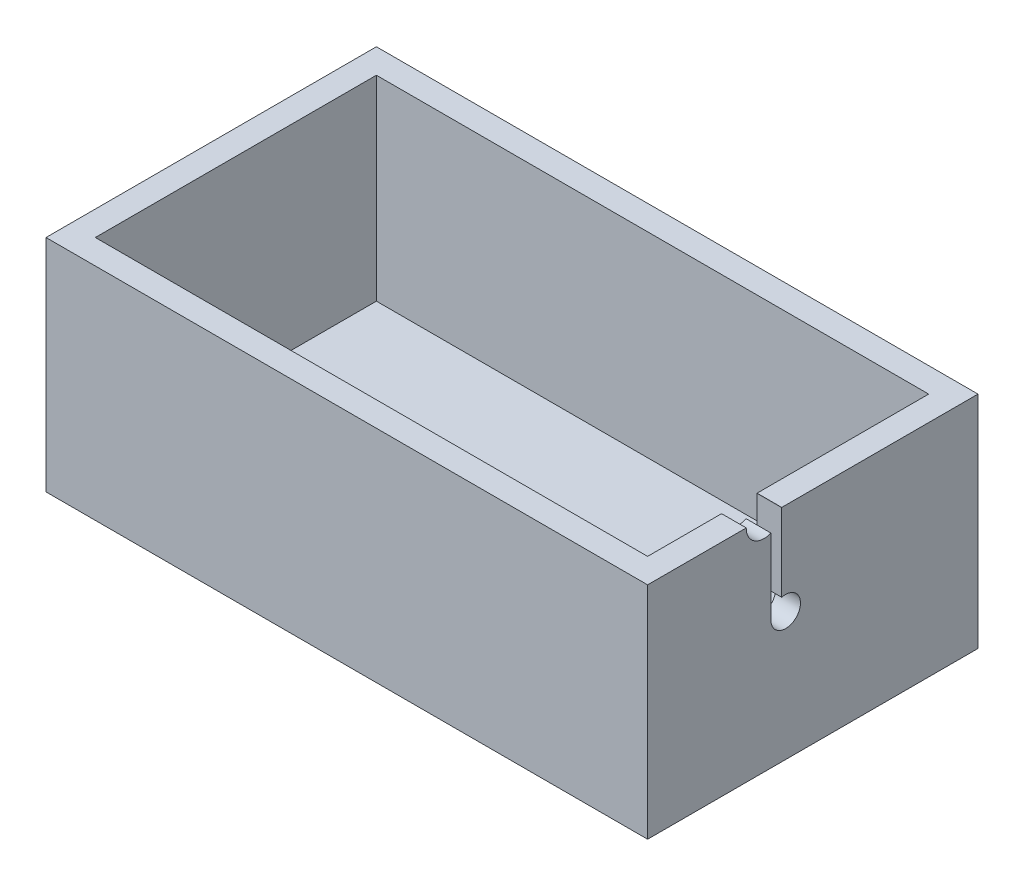
SolidWorks part; units mm, degrees
ref_plane "前视基准面" through (0, 0, 0) normal (0, 0, 1) x (1, 0, 0)
ref_plane "上视基准面" through (0, 0, 0) normal (0, 1, 0) x (1, 0, 0)
ref_plane "右视基准面" through (0, 0, 0) normal (1, 0, 0) x (0, 0, -1)
sketch "草图1" plane through (0, 0, 0) normal (0, 1, 0) x (1, 0, 0)
  line L1 (56, -28.5) -> (-56, -28.5)
  line L2 (56, -28.5) -> (56, 28.5)
  line L3 (56, 28.5) -> (-56, 28.5)
  line L4 (-56, -28.5) -> (-56, 28.5)
  line L5 (56, -28.5) -> (-56, 28.5) construction
  line L6 (56, 28.5) -> (-56, -28.5) construction
  point P0 (0, 0)
  dimension "D1" = 112
  dimension "D2" = 57
extrude "凸台-拉伸1" add sketch "草图1" along normal blind 89
shell "抽壳1" thickness 5 removed face at (0, 89, 0) outward yes
sketch "草图2" plane through (56, 0, 0) normal (1, 0, 0) x (0, 0, -1)
  line L0 (1.2533, 0) -> (-16.4344, 0) construction
  line L1 (-28.5, 89) -> (-28.5, 0) construction
  line L2 (-28.5, 89) -> (-28.5, 0) construction
  line L3 (-8.5, 21) -> (-8.5, 36.2834)
  line L4 (-6.3, 39.6) -> (-6.3, 23.8914)
  arc A0 (-6.3, 39.6) -> (-8.5, 36.2834) centre (-9.9, 39.6) ccw
  arc A1 (-8.5, 21) -> (-6.3, 23.8914) centre (-5.5, 21) ccw
  dimension "D1" = 36
  dimension "D2" = 7.2
  dimension "D5" = 6
  dimension "D3" = 15
  dimension "D4" = 21
  dimension "D6" = 23
extrude "切除-拉伸1" cut sketch "草图2" along normal up to next
sketch "草图3" plane through (61, 0, 0) normal (1, 0, 0) x (0, 0, -1)
  line L0 (33.5, 89) -> (33.5, -5) construction
  line L1 (-33.5, 89) -> (33.5, 89)
  line L2 (-33.5, 89) -> (-33.5, 39.6816)
  line L3 (-33.5, 39.6816) -> (33.5, 39.6816)
  line L4 (33.5, 89) -> (33.5, 39.6816)
extrude "切除-拉伸2" cut sketch "草图3" against normal through all
